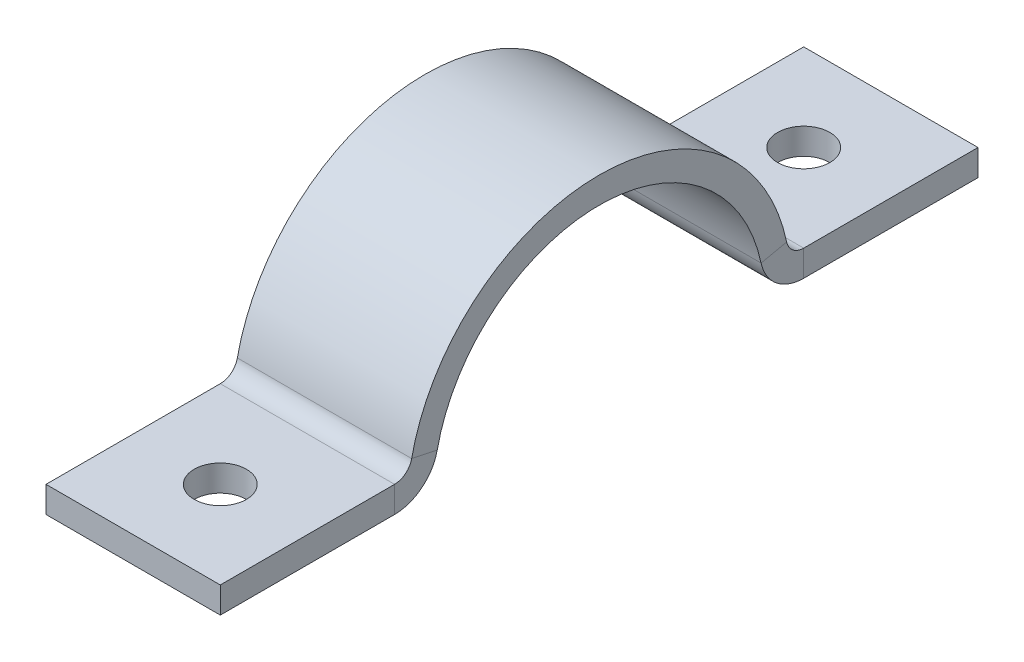
SolidWorks part; units mm, degrees
material "Galvanized Steel"
ref_plane "Front Plane" through (0, 0, 0) normal (0, 0, 1) x (1, 0, 0)
ref_plane "Top Plane" through (0, 0, 0) normal (0, 1, 0) x (1, 0, 0)
ref_plane "Right Plane" through (0, 0, 0) normal (1, 0, 0) x (0, 0, -1)
sketch "Sketch7" plane through (0, 0, 0) normal (1, 0, 0) x (0, 0, -1)
  line L11 (23.4734, 0) -> (43.4734, 0)
  line L14 (-43.4734, 0) -> (-23.4734, 0)
  arc A7 (18.5831, 3.9583) -> (-18.5831, 3.9583) centre (0, 0) ccw
  arc A10 (18.5831, 3.9583) -> (23.4734, 0) centre (23.4734, 5) ccw
  arc A11 (-18.5831, 3.9583) -> (-23.4734, 0) centre (-23.4734, 5) cw
  point P21 (19, 0)
  dimension "D1" = 20
  dimension "D3" = 38
  dimension "D2" = 5
ref_plane "Plane1" through (0, 0, -43.4734) normal (0, 0, 1) x (1, 0, 0)
sketch "Sketch8" plane through (0, 0, -43.4734) normal (0, 0, 1) x (1, 0, 0)
  line L1 (10, 3) -> (-10, 3)
  line L2 (10, 3) -> (10, 0)
  line L3 (10, 0) -> (-10, 0)
  line L4 (-10, 3) -> (-10, 0)
  dimension "D1" = 3
  dimension "D2" = 20
sweep "Sweep1" add profiles "Sketch8" path "Sketch7"
sketch "Sketch10" plane through (0, 0, 0) normal (0, -1, 0) x (-1, 0, 0)
  line L0 (10, -23.4734) -> (-10, -23.4734) construction
  line L1 (10, 23.4734) -> (-10, 23.4734) construction
  circle A0 centre (0, 33.4734) radius 3
  circle A1 centre (0, -33.4734) radius 3
  point P12 (0, -23.4734)
  dimension "D1" = 6
  dimension "D2" = 6
  dimension "D4" = 10
  dimension "D3" = 10
extrude "Cut-Extrude1" cut sketch "Sketch10" against normal through all
